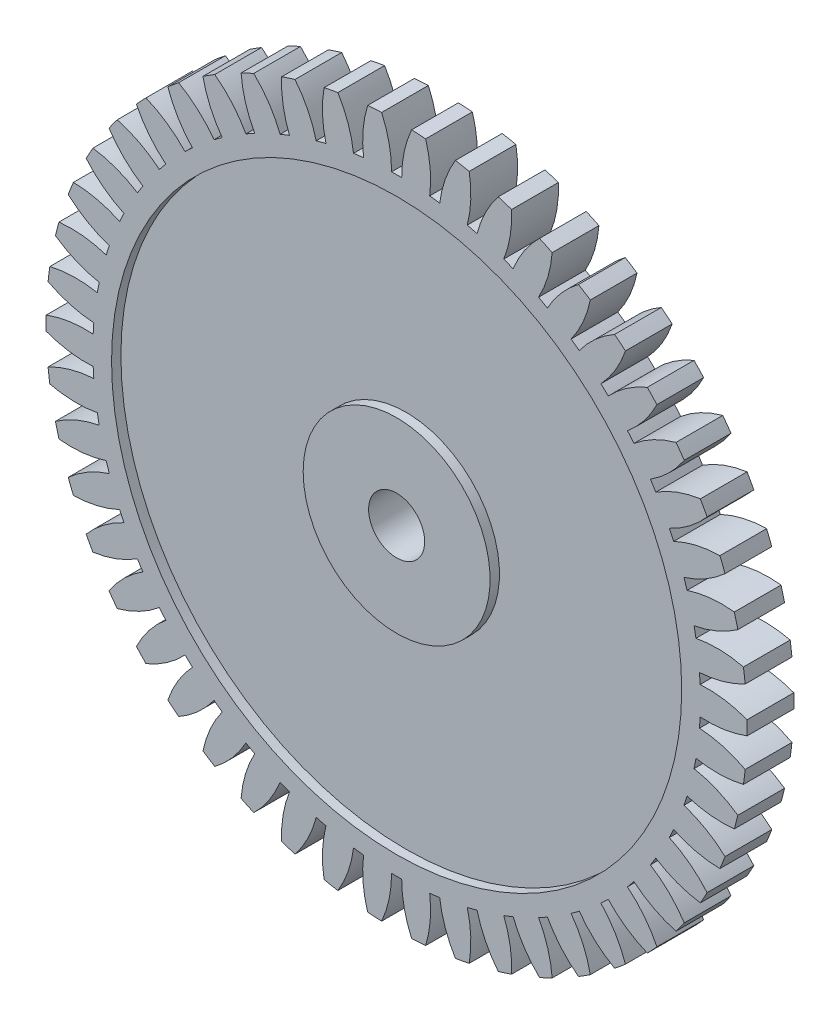
SolidWorks part; units mm, degrees
material "ABS PC"
ref_plane "Front Plane" through (0, 0, 0) normal (0, 0, 1) x (1, 0, 0)
ref_plane "Top Plane" through (0, 0, 0) normal (0, 1, 0) x (1, 0, 0)
ref_plane "Right Plane" through (0, 0, 0) normal (1, 0, 0) x (0, 0, -1)
sketch "Sketch1" plane through (0, 0, 0) normal (0, 0, 1) x (1, 0, 0)
  circle A0 centre (0, 0) radius 6.5
  dimension "D1" = 13
extrude "Extrude1" add sketch "Sketch1" along normal mid plane 1
sketch "Sketch2" plane through (0, 0, 0.5) normal (0, 0, 1) x (1, 0, 0)
  line L0 (-7.5, 0) -> (-6.5, 0) construction
  arc A2 (-6.4931, 0.3) -> (-6.4931, -0.3) centre (0, 0) ccw
  arc A3 (-7.4985, -0.15) -> (-6.4931, -0.3) centre (-6.6497, 2.0949) ccw
  arc A4 (-7.4985, 0.15) -> (-7.4985, -0.15) centre (0, 0) ccw
  arc A5 (-6.4931, 0.3) -> (-7.4985, 0.15) centre (-6.6497, -2.0949) ccw
  circle A12 centre (0, 0) radius 6.5 construction
  point P7 (0, 0)
  dimension "D1" = 1
  dimension "D2" = 2.4
  dimension "D3" = 2.4
  dimension "D4" = 0.3
  dimension "D5" = 0.6
extrude "Extrude2" add sketch "Sketch2" against normal blind 1
pattern_circular "CirPattern1" count 50 over 360 about axis through (0, 0, 0.5) along (0, 0, -1) of "Extrude2"
sketch "Sketch3" plane through (0, 0, -0.5) normal (0, 0, -1) x (-1, 0, 0)
  circle A0 centre (0, 0) radius 2
  circle A1 centre (0, 0) radius 6.1
  dimension "D1" = 4
  dimension "D2" = 12.2
extrude "Cut-Extrude1" cut sketch "Sketch3" against normal blind 0.2
mirror "Mirror1" about plane through (0, 0, 0) normal (0, 0, 1) of "Cut-Extrude1"
sketch "Sketch4" plane through (0, 0, -0.5) normal (0, 0, -1) x (-1, 0, 0)
  line L0 (0, 1.7) -> (0, 0) construction
  arc A0 (-0.2, 1.2339) -> (-0.0737, 1.7985) centre (0.5142, 1.3705) cw
  arc A1 (0.0737, 1.7985) -> (-0.0737, 1.7985) centre (0, 0) ccw
  arc A3 (-0.2, 1.2339) -> (0.2, 1.2339) centre (0, 0) ccw
  arc A6 (0.2, 1.2339) -> (0.0737, 1.7985) centre (-0.5142, 1.3705) ccw
  dimension "D1" = 1.25
  dimension "D2" = 1.8
  dimension "D3" = 0.2
  dimension "D4" = 0.7272
  dimension "D5" = 0.1473
extrude "Extrude3" add sketch "Sketch4" along normal blind 1.5
pattern_circular "CirPattern2" count 14 over 360 of "Extrude3"
sketch "Sketch5" plane through (0, 0, -2) normal (0, 0, -1) x (-1, 0, 0)
  circle A0 centre (0, 0) radius 0.6
  dimension "D1" = 1.2
extrude "Cut-Extrude2" cut sketch "Sketch5" against normal up to surface (2.5 mm away) up to face at (-2, 0, 0.5)
